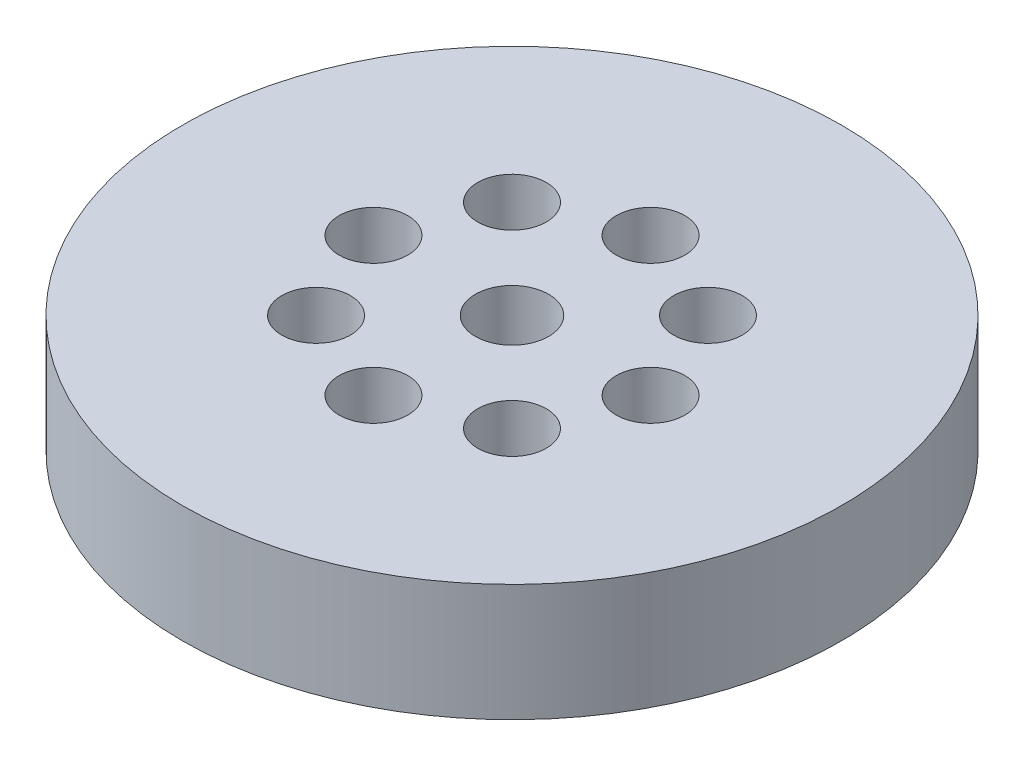
SolidWorks part; units mm, degrees
ref_plane "Front Plane" through (0, 0, 0) normal (0, 0, 1) x (1, 0, 0)
ref_plane "Top Plane" through (0, 0, 0) normal (0, 1, 0) x (1, 0, 0)
ref_plane "Right Plane" through (0, 0, 0) normal (1, 0, 0) x (0, 0, -1)
sketch "Sketch1" plane through (0, 0, 0) normal (0, 1, 0) x (1, 0, 0)
  circle A0 centre (0, 0) radius 45
  dimension "FLANGE_OD" = 90
extrude "Boss-Extrude1" add sketch "Sketch1" along normal blind 16
sketch "Sketch2" plane through (0, 0, 0) normal (0, 1, 0) x (1, 0, 0)
  circle A0 centre (0, 0) radius 5
  dimension "BORE_D" = 10
extrude "Cut-Extrude1" cut sketch "Sketch2" along normal through all
sketch "Sketch3" plane through (0, 16, 0) normal (0, 1, 0) x (1, 0, 0)
  circle A0 centre (0, 0) radius 18.9186 construction
  circle A1 centre (-18.9186, 0) radius 4.6848
  dimension "BOLT_D" = 9.3696
  dimension "BOLT_PCD" = 37.8372
extrude "Cut-Extrude2" cut sketch "Sketch3" against normal blind 9.6191
pattern_circular "CirPattern1" count 8 over 360 about axis through (0, 0, 0) along (0, 1, 0) of "Cut-Extrude2"
